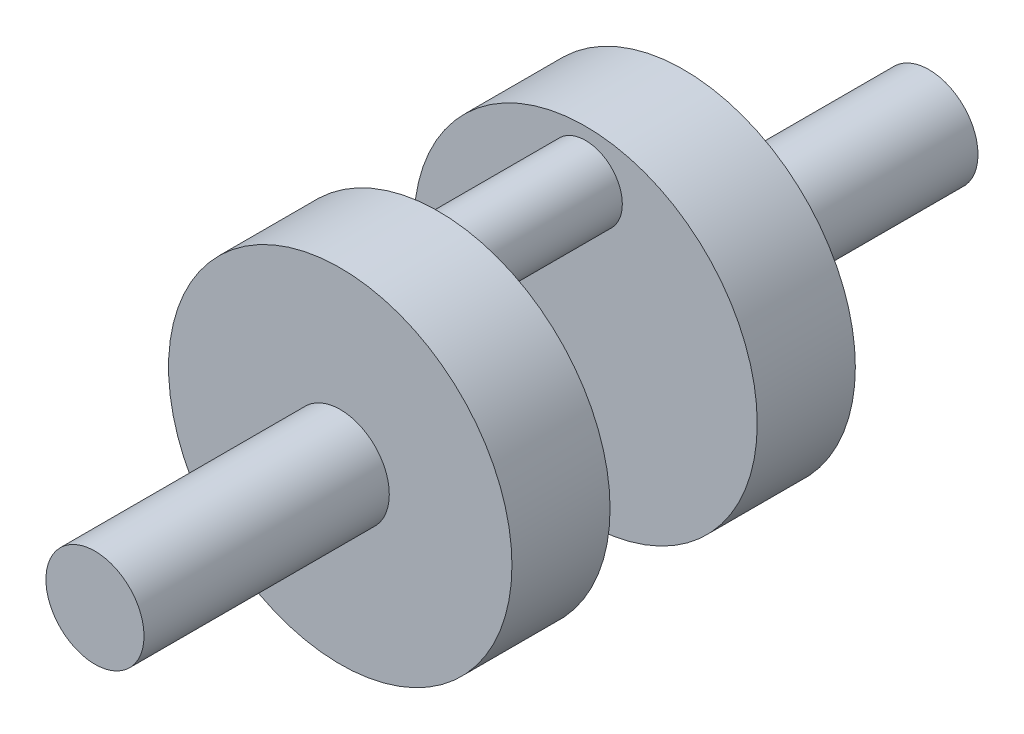
SolidWorks part; units mm, degrees
ref_plane "Front Plane" through (0, 0, 0) normal (0, 0, 1) x (1, 0, 0)
ref_plane "Top Plane" through (0, 0, 0) normal (0, 1, 0) x (1, 0, 0)
ref_plane "Right Plane" through (0, 0, 0) normal (1, 0, 0) x (0, 0, -1)
sketch "Sketch1" plane through (0, 0, 0) normal (0, 0, 1) x (1, 0, 0)
  line L0 (0, 0) -> (0, 25) construction
  circle A0 centre (0, 0) radius 10
  circle A1 centre (0, 0) radius 35
  circle A2 centre (0, 25) radius 7.5
  point P5 (0, 27.2242)
  dimension "D1" = 20
  dimension "D2" = 70
  dimension "D3" = 15
  dimension "D4" = 25
extrude "Boss-Extrude1" add sketch "Sketch1" against normal blind 30 contours A2
extrude "Boss-Extrude2" add sketch "Sketch1<4>" along normal blind 20 contours A2 | A1 A0 A2 region at (-34.0101, 0, 0) region at (0, 25, 0)
sketch "Sketch1<4>" plane through (0, 0, 0) normal (0, 0, 1) x (1, 0, 0) same geometry as "Sketch1"
extrude "Boss-Extrude3" add sketch "Sketch1<5>" against normal blind 20 from surface contours A2 | A1 A0 A2 region at (-34.0101, 0, 0) region at (0, 25, 0) starting at face at (7.5, 25, -30)
sketch "Sketch1<5>" plane through (0, 0, 0) normal (0, 0, 1) x (1, 0, 0) same geometry as "Sketch1"
extrude "Boss-Extrude4" add sketch "Sketch1<6>" along normal blind 70 contours A0
sketch "Sketch1<6>" plane through (0, 0, 0) normal (0, 0, 1) x (1, 0, 0) same geometry as "Sketch1"
extrude "Boss-Extrude5" add sketch "Sketch1<7>" against normal blind 70 from surface contours A0 starting at face at (7.5, 25, -30)
sketch "Sketch1<7>" plane through (0, 0, 0) normal (0, 0, 1) x (1, 0, 0) same geometry as "Sketch1"
